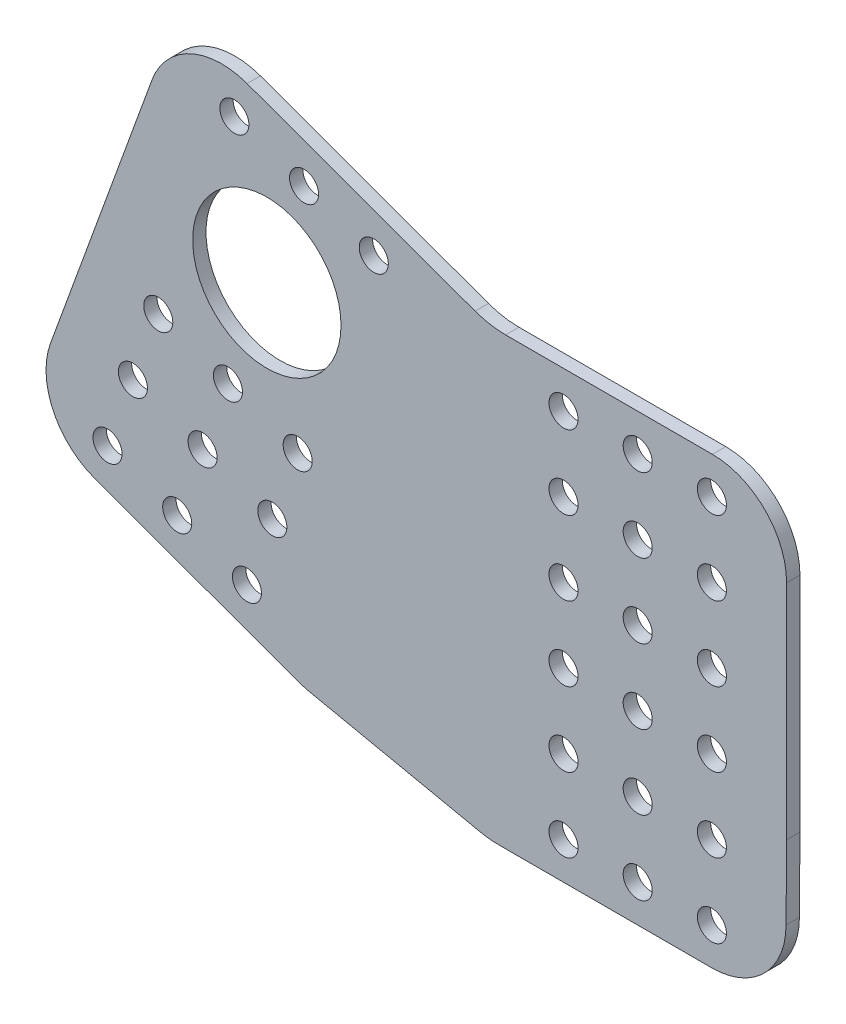
SolidWorks part; units mm, degrees
ref_plane "Front Plane" through (0, 0, 0) normal (0, 0, 1) x (1, 0, 0)
ref_plane "Top Plane" through (0, 0, 0) normal (0, 1, 0) x (1, 0, 0)
ref_plane "Right Plane" through (0, 0, 0) normal (1, 0, 0) x (0, 0, -1)
sketch "Sketch2" plane through (0, 0, 0) normal (0, 0, 1) x (1, 0, 0)
  line L0 (33.4302, 610.9533) -> (33.4302, 560.1533)
  line L1 (33.4302, 610.9533) -> (-17.3698, 610.9533)
  line L2 (-17.3698, 610.9533) -> (-70.8829, 630.4304)
  line L3 (-70.8829, 630.4304) -> (-88.2575, 582.694)
  line L4 (-88.2575, 582.694) -> (-40.5211, 565.3194)
  line L5 (-40.5211, 565.3194) -> (-17.3698, 560.1533)
  line L6 (-17.3698, 560.1533) -> (33.4302, 560.1533)
  line L7 (-70.8829, 630.4304) -> (-76.8499, 632.6022)
  line L8 (-76.8499, 632.6022) -> (-94.2245, 584.8659)
  line L9 (-94.2245, 584.8659) -> (-88.2575, 582.694)
  line L10 (-17.3698, 610.9533) -> (-17.3698, 560.1533)
  line L11 (-40.5211, 565.3194) -> (-23.1465, 613.0558)
  line L12 (33.4302, 610.9533) -> (39.7802, 610.9533)
  line L13 (39.7802, 610.9533) -> (39.7802, 560.1533)
  line L14 (39.7802, 560.1533) -> (33.4302, 560.1533)
  line L15 (-88.2575, 582.694) -> (-92.6011, 570.7599)
  line L16 (-66.5392, 642.3645) -> (-275.0347, 69.5279) construction
  line L17 (-92.6011, 570.7599) -> (-44.8648, 553.3853)
  line L18 (-18.8028, 624.9899) -> (-227.2983, 52.1533) construction
  line L19 (-44.8648, 553.3853) -> (-40.5211, 565.3194)
  line L20 (-17.3698, 560.1533) -> (-17.4643, 547.4533)
  line L21 (-17.4643, 610.9533) -> (-17.4643, -74.8467) construction
  line L22 (-17.4643, 547.4533) -> (33.3357, 547.4533)
  line L23 (33.3357, 610.9533) -> (33.3357, -74.8467) construction
  line L24 (33.3357, 547.4533) -> (33.4302, 560.1533)
  line L25 (-18.8028, 624.9899) -> (-66.5392, 642.3645) construction
  line L27 (-92.6011, 570.7599) -> (-96.9448, 558.8258)
  line L28 (-96.9448, 558.8258) -> (-49.2084, 541.4512)
  line L29 (-49.2084, 541.4512) -> (-44.8648, 553.3853)
  line L30 (-17.4643, 547.4533) -> (-17.4643, 534.7533)
  line L31 (-17.4643, 534.7533) -> (33.3357, 534.7533)
  line L32 (33.3357, 534.7533) -> (33.3357, 547.4533)
  line L33 (-49.2084, 541.4512) -> (-17.4643, 534.7533)
  circle A25 centre (-49.1865, 615.7761) radius 2.4892 construction
  circle A26 centre (-61.1206, 620.1197) radius 2.4892 construction
  circle A27 centre (-49.1865, 615.7761) radius 2.4892
  circle A28 centre (-61.1206, 620.1197) radius 2.4892
  circle A29 centre (-37.2524, 611.4324) radius 2.4892 construction
  circle A30 centre (-50.2834, 575.6301) radius 2.4892 construction
  circle A31 centre (-74.1516, 584.3174) radius 2.4892 construction
  circle A32 centre (-62.2175, 579.9738) radius 2.4892 construction
  circle A33 centre (-54.627, 563.696) radius 2.4892 construction
  circle A34 centre (-66.5611, 568.0397) radius 2.4892 construction
  circle A35 centre (-78.4952, 572.3833) radius 2.4892 construction
  circle A36 centre (-37.2524, 611.4324) radius 2.4892
  circle A37 centre (-50.2834, 575.6301) radius 2.4892
  circle A38 centre (-74.1516, 584.3174) radius 2.4892
  circle A39 centre (-62.2175, 579.9738) radius 2.4892
  circle A40 centre (-54.627, 563.696) radius 2.4892
  circle A41 centre (-66.5611, 568.0397) radius 2.4892
  circle A42 centre (-78.4952, 572.3833) radius 2.4892
  circle A43 centre (-4.7643, 591.9033) radius 2.4892 construction
  circle A44 centre (7.9357, 591.9033) radius 2.4892 construction
  circle A45 centre (20.6357, 591.9033) radius 2.4892 construction
  circle A46 centre (20.6357, 604.6033) radius 2.4892 construction
  circle A47 centre (7.9357, 604.6033) radius 2.4892 construction
  circle A48 centre (-4.7643, 604.6033) radius 2.4892 construction
  circle A49 centre (-4.7643, 591.9033) radius 2.4892
  circle A50 centre (7.9357, 591.9033) radius 2.4892
  circle A51 centre (20.6357, 591.9033) radius 2.4892
  circle A52 centre (20.6357, 604.6033) radius 2.4892
  circle A53 centre (7.9357, 604.6033) radius 2.4892
  circle A54 centre (-4.7643, 604.6033) radius 2.4892
  circle A55 centre (20.6357, 553.8033) radius 2.4892 construction
  circle A56 centre (20.6357, 566.5033) radius 2.4892 construction
  circle A57 centre (7.9357, 566.5033) radius 2.4892 construction
  circle A58 centre (-4.7643, 566.5033) radius 2.4892 construction
  circle A59 centre (-4.7643, 579.2033) radius 2.4892 construction
  circle A60 centre (7.9357, 579.2033) radius 2.4892 construction
  circle A61 centre (20.6357, 579.2033) radius 2.4892 construction
  circle A62 centre (20.6357, 553.8033) radius 2.4892
  circle A63 centre (20.6357, 566.5033) radius 2.4892
  circle A64 centre (7.9357, 566.5033) radius 2.4892
  circle A65 centre (-4.7643, 566.5033) radius 2.4892
  circle A66 centre (-4.7643, 579.2033) radius 2.4892
  circle A67 centre (7.9357, 579.2033) radius 2.4892
  circle A68 centre (20.6357, 579.2033) radius 2.4892
  circle A69 centre (20.6357, 541.1033) radius 2.4892 construction
  circle A70 centre (7.9357, 541.1033) radius 2.4892 construction
  circle A71 centre (-4.7643, 541.1033) radius 2.4892 construction
  circle A72 centre (-58.9707, 551.7619) radius 2.4892 construction
  circle A73 centre (-70.9048, 556.1056) radius 2.4892 construction
  circle A74 centre (-82.8389, 560.4492) radius 2.4892 construction
  circle A75 centre (-4.7643, 553.8033) radius 2.4892 construction
  circle A76 centre (7.9357, 553.8033) radius 2.4892 construction
  circle A77 centre (20.6357, 541.1033) radius 2.4892
  circle A78 centre (7.9357, 541.1033) radius 2.4892
  circle A79 centre (-4.7643, 541.1033) radius 2.4892
  circle A80 centre (-58.9707, 551.7619) radius 2.4892
  circle A81 centre (-70.9048, 556.1056) radius 2.4892
  circle A82 centre (-82.8389, 560.4492) radius 2.4892
  circle A83 centre (-4.7643, 553.8033) radius 2.4892
  circle A84 centre (7.9357, 553.8033) radius 2.4892
  circle A85 centre (-55.563, 598.2568) radius 12.7 construction
  circle A86 centre (-55.563, 598.2568) radius 12.7
  dimension "D3" = 12.7
  dimension "D6" = 12.7
  dimension "D1" = 50.8
  dimension "D17" = 50.8
  dimension "D18" = 6.35
  dimension "D19" = 6.35
  dimension "D20" = 6.35
  dimension "D21" = 6.35
  dimension "D22" = 50.8
  dimension "D48" = 12.7
  dimension "D49" = 12.7
  dimension "D50" = 12.7
extrude "Boss-Extrude1" add sketch "Sketch2" along normal blind 2.286 contours L4 L11 L2 L3 | L11 L5 L10 L2 | L1 L10 L6 L0 A41 A39 A37 A28 | L17 L19 L4 L15 A54 A52 | L22 L24 L6 L20 | L28 L29 L17 L27 A82 A81 A80 | L31 L32 L22 L30 A79 A78 A77 | L29 L33 L30 L20 L5 L19 region at (8.0396, 585.5533, 0) region at (32.8584, 553.8072, 0) region at (-25.4909, 582.5086, 0) region at (-31.2956, 549.7891, 0) region at (32.8121, 541.1033, 0) region at (-32.6991, 589.5025, 0) region at (-43.2545, 559.5568, 0) region at (-47.5982, 547.6227, 0)
fillet "Fillet6" radius 12.7 4 edges at (-70.8829, 630.4304, 1.143) (-96.9448, 558.8258, 1.143) (33.4302, 610.9533, 1.143) (33.3357, 534.7533, 1.143)
fillet "Fillet7" radius 15.24 3 edges at (-49.2084, 541.4512, 1.143) (-17.4643, 534.7533, 1.143) (-17.3698, 610.9533, 1.143)
